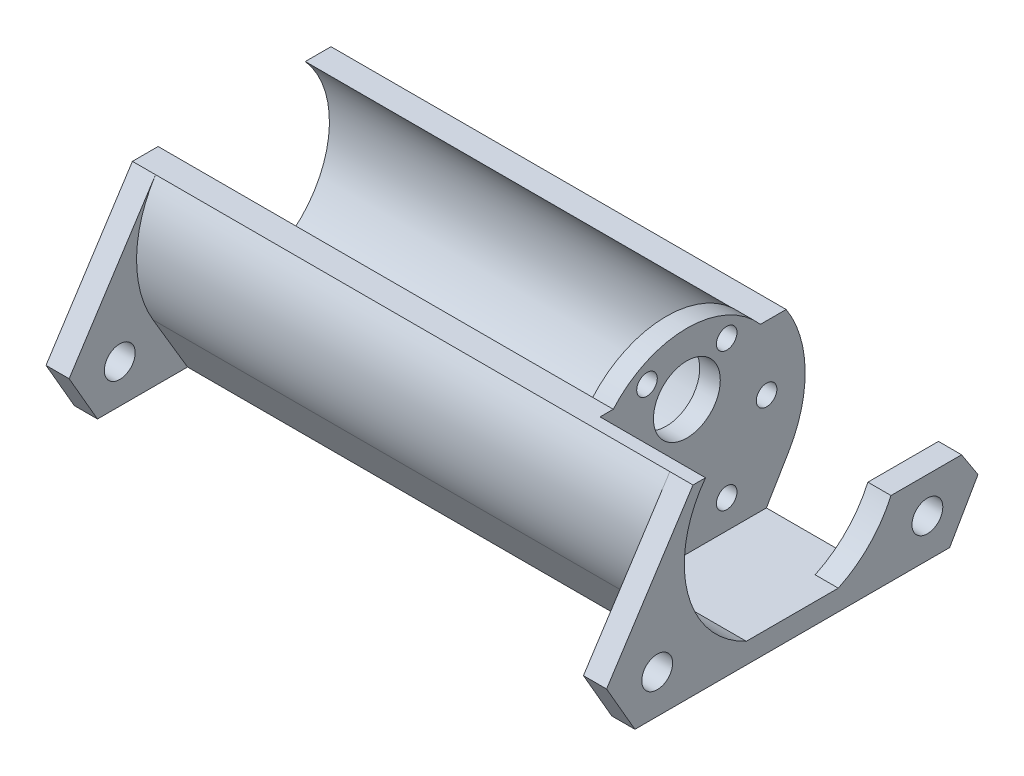
SolidWorks part; units mm, degrees
ref_plane "Front Plane" through (0, 0, 0) normal (0, 0, 1) x (1, 0, 0)
ref_plane "Top Plane" through (0, 0, 0) normal (0, 1, 0) x (1, 0, 0)
ref_plane "Right Plane" through (0, 0, 0) normal (1, 0, 0) x (0, 0, -1)
sketch "Sketch1" plane through (0, 0, 0) normal (1, 0, 0) x (0, 0, -1)
  line L0 (26.2679, -23) -> (0, -23)
  line L1 (0, -23) -> (-26.2679, -23)
  line L2 (26.2679, -23) -> (30.598, -23)
  line L3 (30.598, -23) -> (36.1099, -13.4531)
  line L4 (36.1099, -13.4531) -> (19.3067, 12.5)
  line L5 (19.3067, 12.5) -> (14.3091, 12.5)
  line L6 (0, 0) -> (26.2679, -15.5) construction
  line L7 (0, 55) -> (0, -55) construction
  line L8 (-26.2679, -23) -> (-30.598, -23)
  line L9 (-30.598, -23) -> (-36.1099, -13.4531)
  line L10 (-36.1099, -13.4531) -> (-19.3067, 12.5)
  line L11 (-19.3067, 12.5) -> (-14.3091, 12.5)
  circle A0 centre (0, 0) radius 23 construction
  circle A1 centre (26.2679, -15.5) radius 7.5 construction
  circle A2 centre (-26.2679, -15.5) radius 7.5 construction
  arc A3 (-14.3091, 12.5) -> (14.3091, 12.5) centre (0, 0) ccw
  circle A4 centre (26.2679, -15.5) radius 3
  circle A5 centre (-26.2679, -15.5) radius 3
  dimension "D1" = 46
  dimension "D2" = 15
  dimension "D3" = 6
  dimension "D4" = 38
  dimension "D7" = 6
  dimension "D5" = 60
  dimension "D6" = 12.5
extrude "Boss-Extrude1" add sketch "Sketch1" along normal mid plane 109
sketch "Sketch2" plane through (0, 0, 0) normal (1, 0, 0) x (0, 0, -1)
  line L0 (26.2679, -15.5) -> (0, 0) construction
  line L2 (36.1099, -13.4531) -> (19.3067, 12.5) construction
  line L3 (19.8085, -11.6885) -> (13.0894, -23)
  line L4 (-30.598, -23) -> (30.598, -23) construction
  line L5 (13.0894, -23) -> (30.598, -23)
  line L6 (30.598, -23) -> (36.1099, -13.4531)
  line L7 (36.1099, -13.4531) -> (19.3067, 12.5)
  line L8 (0, 25.3) -> (0, -25.3) construction
  line L9 (-19.8085, -11.6885) -> (-13.0894, -23)
  line L10 (-13.0894, -23) -> (-30.598, -23)
  line L11 (-30.598, -23) -> (-36.1099, -13.4531)
  line L12 (-36.1099, -13.4531) -> (-19.3067, 12.5)
  circle A0 centre (0, 0) radius 23 construction
  circle A1 centre (26.2679, -15.5) radius 7.5 construction
  arc A2 (19.3067, 12.5) -> (19.8085, -11.6885) centre (0, 0) cw
  arc A3 (-19.3067, 12.5) -> (-19.8085, -11.6885) centre (0, 0) ccw
  dimension "D1" = 46
extrude "Cut-Extrude1" cut sketch "Sketch2" against normal mid plane 100
sketch "Sketch3" plane through (0, 0, 0) normal (1, 0, 0) x (0, 0, -1)
  circle A0 centre (0, 0) radius 19
  circle A1 centre (0, 7) radius 6.5
  circle A2 centre (15.5, 0) radius 2
  circle A3 centre (7.75, -13.4234) radius 2
  circle A4 centre (-7.75, -13.4234) radius 2
  circle A5 centre (-15.5, 0) radius 2
  circle A6 centre (-7.75, 13.4234) radius 2
  circle A7 centre (7.75, 13.4234) radius 2
  dimension "D1" = 7
  dimension "D2" = 13
  dimension "D3" = 4
  dimension "D4" = 15.5
  dimension "D5" = 6
extrude "Boss-Extrude2" add sketch "Sketch3" along normal blind 4 from offset 30
sketch "Sketch4" plane through (34, 0, 0) normal (1, 0, 0) x (0, 0, -1)
  line L5 (-8.9443, -19) -> (8.9443, -19)
  line L6 (32.9181, -8.5233) -> (19.1925, -8.5233)
  line L7 (36.1099, -13.4531) -> (19.3067, 12.5) construction
  line L8 (32.9181, -8.5233) -> (19.3067, 12.5)
  line L9 (19.3067, 12.5) -> (16.8079, 12.5)
  line L10 (19.3067, 12.5) -> (14.3091, 12.5) construction
  circle A3 centre (0, 0) radius 21
  circle M8 centre (-7.75, 13.4234) radius 2
  circle M9 centre (-7.75, -13.4234) radius 2
  circle M10 centre (15.5, 0) radius 2
  arc M11 (14.3091, 12.5) -> (-14.3091, 12.5) centre (0, 0) ccw
  arc M12 (-14.3091, 12.5) -> (14.3091, 12.5) centre (0, 0) ccw
  circle M13 centre (0, 7) radius 6.5
  circle M14 centre (7.75, -13.4234) radius 2
  circle M15 centre (-15.5, 0) radius 2
  circle M16 centre (7.75, 13.4234) radius 2
  dimension "D1" = 42
  dimension "D2" = 19
extrude "Cut-Extrude2" cut sketch "Sketch4" along normal through all contours M12 M11 M9 M14 M16 M15 M13 M10 M8 | A3 L5 M12 M11 | A3 L6 L8 L9 region at (34, -1.0034, 0) region at (34, 12.9445, 15.7929) region at (34, -1.2766, -24.2127)
sketch "Sketch5" plane through (34, 0, 0) normal (1, 0, 0) x (0, 0, -1)
  line L0 (8.9443, -19) -> (40.5968, -19)
  line L1 (40.5968, -19) -> (40.5968, 3.1995)
  line L2 (40.5968, 3.1995) -> (8.9443, 3.1995)
  line L3 (8.9443, 3.1995) -> (8.9443, -19)
extrude "Cut-Extrude3" cut sketch "Sketch5" along direction (-1, 0, 0) on the side of the normal up to surface (16 mm away) up to face at (50, -14.703, -25.6578)
